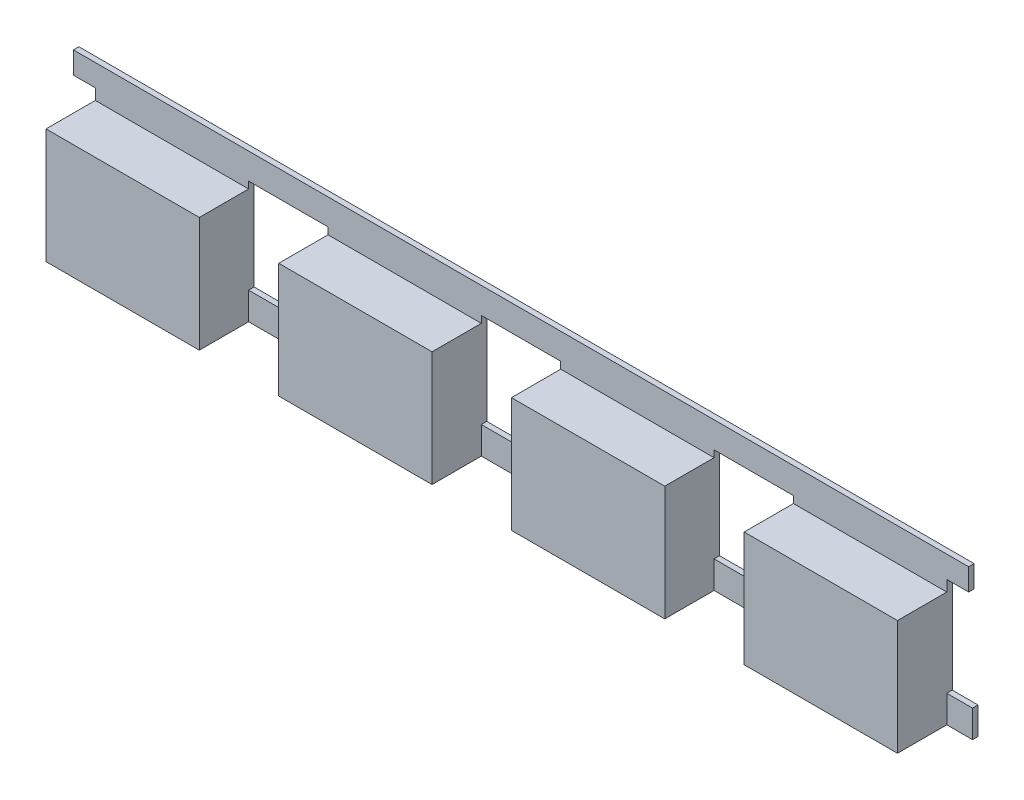
SolidWorks part; units mm, degrees
ref_plane "Спереди" through (0, 0, 0) normal (0, 0, 1) x (1, 0, 0)
ref_plane "Сверху" through (0, 0, 0) normal (0, 1, 0) x (1, 0, 0)
ref_plane "Справа" through (0, 0, 0) normal (1, 0, 0) x (0, 0, -1)
other "Configuration Table"
sketch "Эскиз1" plane through (0, 0, 0) normal (0, 0, 1) x (1, 0, 0)
  line L1 (-2.8, -2.1) -> (2.8, -2.1)
  line L2 (-2.8, -2.1) -> (-2.8, 2.1)
  line L3 (-2.8, 2.1) -> (2.8, 2.1)
  line L4 (2.8, -2.1) -> (2.8, 2.1)
  line L5 (-2.8, -2.1) -> (2.8, 2.1) construction
  line L6 (-2.8, 2.1) -> (2.8, -2.1) construction
  point P0 (0, 0)
  dimension "D1" = 4.2
  dimension "D2" = 5.6
extrude "Бобышка-Вытянуть1" add sketch "Эскиз1" along normal blind 1.4
sketch "Эскиз2" plane through (0, 0, 1.4) normal (0, 0, 1) x (1, 0, 0)
  line L0 (0, 0) -> (-1.0279, 0)
sketch "Эскиз3" plane through (0, 0, 0) normal (0, 0, -1) x (-1, 0, 0)
  line L1 (2.8, 2.1) -> (-28.3, 2.1)
  line L2 (2.8, 2.1) -> (2.8, 3.3)
  line L3 (2.8, 3.3) -> (-28.3, 3.3)
  line L4 (-28.3, 2.1) -> (-28.3, 3.3)
  line L5 (2.8, 2.1) -> (-28.3, 2.1)
  line L6 (2.8, 2.1) -> (2.8, 1.8)
  line L7 (2.8, 1.8) -> (-28.3, 1.8)
  line L8 (-28.3, 2.1) -> (-28.3, 1.8)
  line M5 (-2.8, 2.1) -> (-2.8, -2.1)
  line M7 (2.8, -2.1) -> (2.8, 2.1)
  line M8 (2.8, 2.1) -> (-2.8, 2.1)
  dimension "D1" = 1.2
  dimension "D2" = 0.3
  dimension "D3" = 31.1
  dimension "D4" = 31.1
extrude "Бобышка-Вытянуть2" add sketch "Эскиз3" against normal blind 0.2 contours L4 L1 L2 L3 M8 | L1 L8 L7 M5 | L7 M7 M8 M5 region at (0, 1.95, 0) region at (12.75, 2.7, 0) region at (15.55, 1.95, 0)
pattern_linear "Линейный массив1" count 4 spacing 8.5 along (1, 0, 0) of "Бобышка-Вытянуть1"
sketch "Эскиз4" plane through (0, 0, 0) normal (0, 0, -1) x (-1, 0, 0)
  line L0 (-22.7, 1.8) -> (-19.8, 1.8)
  line L2 (-22.7, 2.35) -> (-19.8, 2.35)
  line L3 (-22.7, 2.35) -> (-22.7, 1.25)
  line L4 (-22.7, 1.25) -> (-19.8, 1.25)
  line L5 (-19.8, 2.35) -> (-19.8, 1.25)
  line L6 (-22.7, 2.35) -> (-19.8, 1.25) construction
  line L7 (-22.7, 1.25) -> (-19.8, 2.35) construction
  line L8 (-14.2, 2.35) -> (-14.2, 1.25)
  line L9 (-14.2, 2.35) -> (-11.3, 2.35)
  line L10 (-11.3, 2.35) -> (-11.3, 1.25)
  line L11 (-14.2, 1.25) -> (-11.3, 1.25)
  line L12 (-5.7, 2.35) -> (-5.7, 1.25)
  line L13 (-5.7, 2.35) -> (-2.8, 2.35)
  line L14 (-2.8, 2.35) -> (-2.8, 1.25)
  line L15 (-5.7, 1.25) -> (-2.8, 1.25)
  point P4 (-21.25, 1.8)
  dimension "D1" = 1.1
  dimension "D2" = 3
extrude "Вырез-Вытянуть1" cut sketch "Эскиз4" against normal blind 0.2 contours L12 L15 L14 L13 | L8 L11 L10 L9 | L5 L0 L4 | L5 L2 L3 L0 region at (21.25, 2.075, 0) region at (21.25, 1.525, 0) region at (12.75, 1.8, 0) region at (4.25, 1.8, 0)
sketch "Эскиз5" plane through (28.3, 0, 0) normal (1, 0, 0) x (0, 0, -1)
  line L0 (0, -2.1) -> (0, 3.3) construction
  line L1 (-0.2, 3.3) -> (0, 3.3)
  line L2 (-0.2, 3.3) -> (-0.2, 2.5)
  line L3 (-0.2, 2.5) -> (0, 2.5)
  line L4 (0, 3.3) -> (0, 2.5)
  dimension "D1" = 0.8
extrude "Бобышка-Вытянуть3" add sketch "Эскиз5" along normal blind 0.8
sketch "Эскиз6" plane through (-2.8, 0, 0) normal (-1, 0, 0) x (0, 0, 1)
  line L0 (0.2, 2.1) -> (0.2, 3.3) construction
  line L1 (0, 3.3) -> (0.2, 3.3)
  line L2 (0, 3.3) -> (0, 2.5)
  line L3 (0, 2.5) -> (0.2, 2.5)
  line L4 (0.2, 3.3) -> (0.2, 2.5)
  dimension "D1" = 0.8
extrude "Бобышка-Вытянуть4" add sketch "Эскиз6" along normal blind 0.8
sketch "Эскиз7" plane through (0, 0, 0) normal (0, 0, -1) x (-1, 0, 0)
  line L1 (-29.2405, -2.1) -> (3.6437, -2.1)
  line L2 (-29.2405, -2.1) -> (-29.2405, -1.1)
  line L3 (-29.2405, -1.1) -> (3.6437, -1.1)
  line L4 (3.6437, -2.1) -> (3.6437, -1.1)
  dimension "D1" = 1
extrude "Бобышка-Вытянуть5" add sketch "Эскиз7" against normal blind 0.2
sketch "Эскиз8" plane through (0, 0, 1.4) normal (0, 0, 1) x (1, 0, 0)
  line L0 (28.3, -2.1) -> (28.3, 2.1) construction
  line L1 (28.3, 2.1) -> (22.7, 2.1) construction
  line L2 (22.7, 2.1) -> (22.7, -2.1) construction
  line L3 (22.7, -2.1) -> (28.3, -2.1) construction
  line L4 (19.8, -2.1) -> (19.8, 2.1) construction
  line L5 (19.8, 2.1) -> (14.2, 2.1) construction
  line L6 (14.2, 2.1) -> (14.2, -2.1) construction
  line L7 (14.2, -2.1) -> (19.8, -2.1) construction
  line L8 (11.3, -2.1) -> (11.3, 2.1) construction
  line L9 (11.3, 2.1) -> (5.7, 2.1) construction
  line L10 (5.7, 2.1) -> (5.7, -2.1) construction
  line L11 (5.7, -2.1) -> (11.3, -2.1) construction
  line L12 (2.8, -2.1) -> (2.8, 2.1) construction
  line L13 (2.8, 2.1) -> (-2.8, 2.1) construction
  line L14 (-2.8, 2.1) -> (-2.8, -2.1) construction
  line L15 (-2.8, -2.1) -> (2.8, -2.1) construction
  line L16 (28.3, -2.1) -> (28.3, 2.1)
  line L17 (28.3, 2.1) -> (22.7, 2.1)
  line L18 (22.7, 2.1) -> (22.7, -2.1)
  line L19 (22.7, -2.1) -> (28.3, -2.1)
  line L20 (19.8, -2.1) -> (19.8, 2.1)
  line L21 (19.8, 2.1) -> (14.2, 2.1)
  line L22 (14.2, 2.1) -> (14.2, -2.1)
  line L23 (14.2, -2.1) -> (19.8, -2.1)
  line L24 (11.3, -2.1) -> (11.3, 2.1)
  line L25 (11.3, 2.1) -> (5.7, 2.1)
  line L26 (5.7, 2.1) -> (5.7, -2.1)
  line L27 (5.7, -2.1) -> (11.3, -2.1)
  line L28 (2.8, -2.1) -> (2.8, 2.1)
  line L29 (2.8, 2.1) -> (-2.8, 2.1)
  line L30 (-2.8, 2.1) -> (-2.8, -2.1)
  line L31 (-2.8, -2.1) -> (2.8, -2.1)
  line L32 (11.9, -2.7) -> (11.9, 2.7)
  line L33 (11.9, 2.7) -> (5.1, 2.7)
  line L34 (5.1, 2.7) -> (5.1, -2.7)
  line L35 (5.1, -2.7) -> (11.9, -2.7)
  line L36 (20.4, -2.7) -> (20.4, 2.7)
  line L37 (20.4, 2.7) -> (13.6, 2.7)
  line L38 (13.6, 2.7) -> (13.6, -2.7)
  line L39 (13.6, -2.7) -> (20.4, -2.7)
  line L40 (28.9, -2.7) -> (28.9, 2.7)
  line L41 (28.9, 2.7) -> (22.1, 2.7)
  line L42 (22.1, 2.7) -> (22.1, -2.7)
  line L43 (22.1, -2.7) -> (28.9, -2.7)
  line L44 (3.4, -2.7) -> (3.4, 2.7)
  line L45 (3.4, 2.7) -> (-3.4, 2.7)
  line L46 (-3.4, 2.7) -> (-3.4, -2.7)
  line L47 (-3.4, -2.7) -> (3.4, -2.7)
  line L48 (2.2, -1.5) -> (2.2, 1.5)
  line L49 (2.2, 1.5) -> (-2.2, 1.5)
  line L50 (-2.2, 1.5) -> (-2.2, -1.5)
  line L51 (-2.2, -1.5) -> (2.2, -1.5)
  line L52 (10.7, -1.5) -> (10.7, 1.5)
  line L53 (10.7, 1.5) -> (6.3, 1.5)
  line L54 (6.3, 1.5) -> (6.3, -1.5)
  line L55 (6.3, -1.5) -> (10.7, -1.5)
  line L56 (19.2, -1.5) -> (19.2, 1.5)
  line L57 (19.2, 1.5) -> (14.8, 1.5)
  line L58 (14.8, 1.5) -> (14.8, -1.5)
  line L59 (14.8, -1.5) -> (19.2, -1.5)
  line L60 (27.7, -1.5) -> (27.7, 1.5)
  line L61 (27.7, 1.5) -> (23.3, 1.5)
  line L62 (23.3, 1.5) -> (23.3, -1.5)
  line L63 (23.3, -1.5) -> (27.7, -1.5)
  dimension "D1" = 0.6
  dimension "D2" = 0.6
extrude "Вырез-Вытянуть2" cut sketch "Эскиз8" against normal blind 1 from offset 1 contours L50 L51 L48 L49 | L54 L55 L52 L53 | L58 L59 L56 L57 | L62 L63 L60 L61 region at (0, 0, 1.4) region at (8.5, 0, 1.4) region at (17, 0, 1.4) region at (25.5, 0, 1.4) offset against normal yes
sketch "Эскиз9" plane through (0, 0, 1.4) normal (0, 0, 1) x (1, 0, 0)
  line L4 (2.8, -2.1) -> (2.8, 2.1)
  line L5 (2.8, 2.1) -> (-2.8, 2.1)
  line L6 (-2.8, 2.1) -> (-2.8, -2.1)
  line L7 (-2.8, -2.1) -> (2.8, -2.1)
  line L8 (2.8, -2.1) -> (2.8, 2.1)
  line L9 (2.8, 2.1) -> (-2.8, 2.1)
  line L10 (-2.8, 2.1) -> (-2.8, -2.1)
  line L11 (-2.8, -2.1) -> (2.8, -2.1)
  line L12 (11.3, -2.1) -> (11.3, 2.1)
  line L13 (11.3, 2.1) -> (5.7, 2.1)
  line L14 (5.7, 2.1) -> (5.7, -2.1)
  line L15 (5.7, -2.1) -> (11.3, -2.1)
  line L16 (11.3, -2.1) -> (11.3, 2.1)
  line L17 (11.3, 2.1) -> (5.7, 2.1)
  line L18 (5.7, 2.1) -> (5.7, -2.1)
  line L19 (5.7, -2.1) -> (11.3, -2.1)
  line L20 (19.8, -2.1) -> (19.8, 2.1)
  line L21 (19.8, 2.1) -> (14.2, 2.1)
  line L22 (14.2, 2.1) -> (14.2, -2.1)
  line L23 (14.2, -2.1) -> (19.8, -2.1)
  line L24 (19.8, -2.1) -> (19.8, 2.1)
  line L25 (19.8, 2.1) -> (14.2, 2.1)
  line L26 (14.2, 2.1) -> (14.2, -2.1)
  line L27 (14.2, -2.1) -> (19.8, -2.1)
  line L28 (28.3, -2.1) -> (28.3, 2.1)
  line L29 (28.3, 2.1) -> (22.7, 2.1)
  line L30 (22.7, 2.1) -> (22.7, -2.1)
  line L31 (22.7, -2.1) -> (28.3, -2.1)
  line L32 (28.3, -2.1) -> (28.3, 2.1)
  line L33 (28.3, 2.1) -> (22.7, 2.1)
  line L34 (22.7, 2.1) -> (22.7, -2.1)
  line L35 (22.7, -2.1) -> (28.3, -2.1)
  dimension "D1" = 0
  dimension "D2" = 0
  dimension "D3" = 0
  dimension "D4" = 0
extrude "Бобышка-Вытянуть6" add sketch "Эскиз9" along normal blind 0.6
